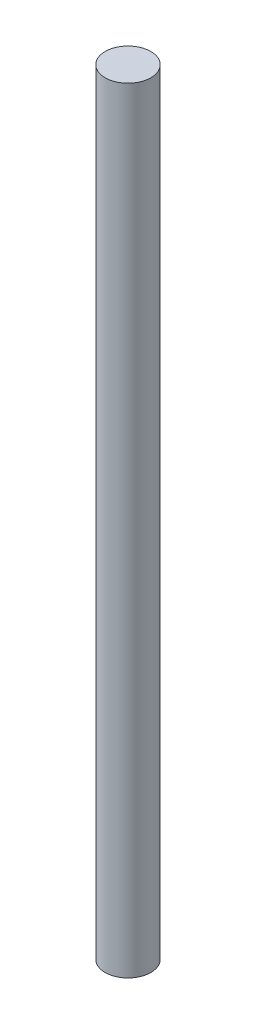
SolidWorks part; units mm, degrees
ref_plane "Front Plane" through (0, 0, 0) normal (0, 0, 1) x (1, 0, 0)
ref_plane "Top Plane" through (0, 0, 0) normal (0, 1, 0) x (1, 0, 0)
ref_plane "Right Plane" through (0, 0, 0) normal (1, 0, 0) x (0, 0, -1)
sketch "Sketch3" plane through (0, 0, 0) normal (0, 1, 0) x (1, 0, 0)
  circle A0 centre (0, 0) radius 5.005
  dimension "D1" = 10.01
extrude "Boss-Extrude1" add sketch "Sketch3" along normal blind 170
